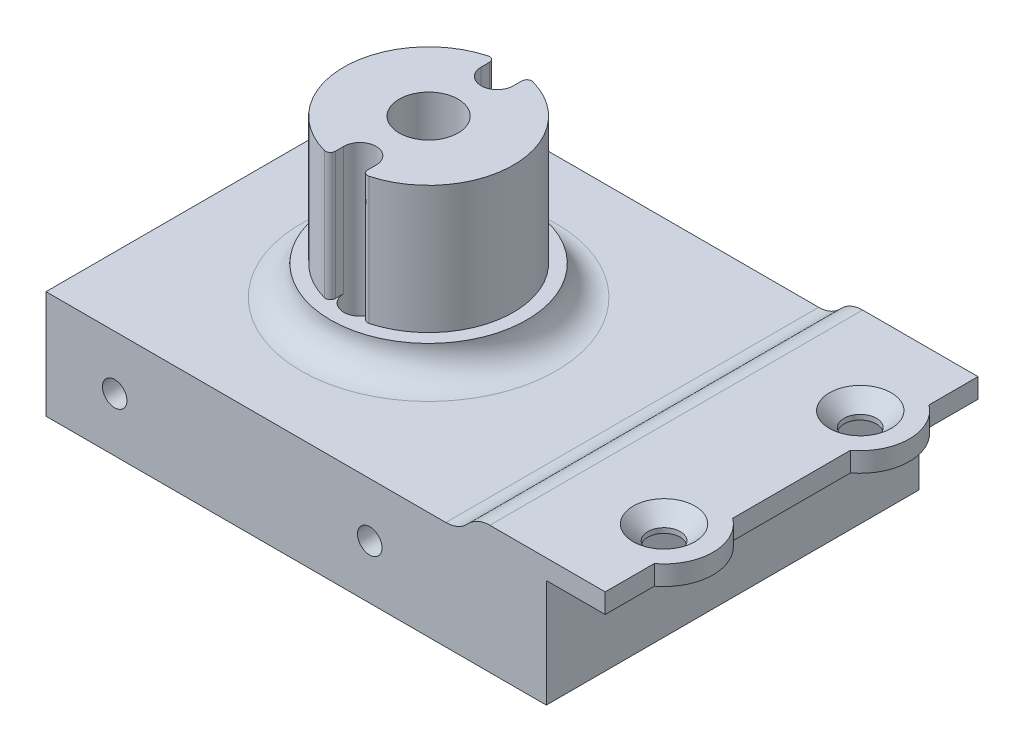
SolidWorks part; units mm, degrees
ref_plane "Спереди" through (0, 0, 0) normal (0, 0, 1) x (1, 0, 0)
ref_plane "Сверху" through (0, 0, 0) normal (0, 1, 0) x (1, 0, 0)
ref_plane "Справа" through (0, 0, 0) normal (1, 0, 0) x (0, 0, -1)
sketch "Эскиз6" plane through (0, 0, 0) normal (0, 1, 0) x (1, 0, 0)
  line L0 (-20, 0) -> (31, 0) construction
  line L1 (-20, -19) -> (31, -19)
  line L2 (-20, -19) -> (-20, 19)
  line L3 (-20, 19) -> (31, 19)
  line L4 (31, -19) -> (31, 19)
  line L5 (0, -19) -> (0, 19) construction
  dimension "D1" = 31
  dimension "D2" = 20
  dimension "D3" = 38
extrude "тело" add sketch "Эскиз6" along normal blind 11
sketch "Эскиз10" plane through (0, 11, 0) normal (0, 1, 0) x (1, 0, 0)
  circle A0 centre (0, 0) radius 10
  dimension "D1" = 20
extrude "основание оси" add sketch "Эскиз10" along normal blind 3
fillet "Скругление1" radius 3 1 edges at (0, 11, -10)
sketch "Эскиз13" plane through (0, 0, 19) normal (0, 0, 1) x (1, 0, 0)
  line L0 (31, 5.5) -> (-13, 5.5) construction
  line L1 (31, 11) -> (31, 0) construction
  line L2 (0, 0) -> (0, 11) construction
  line L3 (-20, 11) -> (31, 11) construction
  circle A0 centre (-13, 5.5) radius 1.25
  circle A1 centre (13, 5.5) radius 1.25
  dimension "D1" = 2.5
  dimension "D2" = 26
  dimension "D3" = 18
extrude "отверстия под шурупы" cut sketch "Эскиз13" against normal through all
sketch "Эскиз15" plane through (0, 14, 0) normal (0, 1, 0) x (1, 0, 0)
  circle A0 centre (0, 0) radius 8.65
  dimension "D1" = 17.3
extrude "ось" add sketch "Эскиз15" along normal blind 13
sketch "Эскиз16" plane through (0, 27, 0) normal (0, 1, 0) x (1, 0, 0)
  line L0 (-7, 1.65) -> (-8.4912, 1.65) construction
  line L1 (-7, -1.65) -> (-8.4912, -1.65) construction
  line L2 (-1.65, 7) -> (-1.65, 8.4912)
  line L3 (1.65, 7) -> (1.65, 8.4912)
  line L4 (7, 1.65) -> (8.4912, 1.65) construction
  line L5 (7, -1.65) -> (8.4912, -1.65) construction
  line L6 (1.65, -7) -> (1.65, -8.4912)
  line L8 (-1.65, -7) -> (-1.65, -8.4912)
  circle A0 centre (0, 0) radius 7 construction
  arc A1 (-1.65, 7) -> (1.65, 7) centre (0, 7) ccw
  arc A2 (7, 1.65) -> (7, -1.65) centre (7, 0) ccw construction
  arc A3 (1.65, -7) -> (-1.65, -7) centre (0, -7) ccw
  arc A4 (-7, -1.65) -> (-7, 1.65) centre (-7, 0) ccw construction
  arc A5 (-8.4912, 1.65) -> (-8.4912, -1.65) centre (0, 0) ccw construction
  circle A6 centre (0, 0) radius 8.65 construction
  arc A7 (1.65, 8.4912) -> (-1.65, 8.4912) centre (0, 0) ccw
  arc A8 (8.4912, -1.65) -> (8.4912, 1.65) centre (0, 0) ccw construction
  arc A9 (-1.65, -8.4912) -> (1.65, -8.4912) centre (0, 0) ccw
  dimension "D1" = 14
  dimension "D2" = 1.65
extrude "крепление к серве" cut sketch "Эскиз16" against normal up to surface (13 mm away) up to face at (0, 14, 8.65)
sketch "Эскиз26" plane through (0, 14, 0) normal (0, 1, 0) x (1, 0, 0)
  circle A0 centre (0, 7) radius 1.65
  circle A1 centre (0, -7) radius 1.65
  arc A2 (1.65, -7) -> (-1.65, -7) centre (0, -7) ccw construction
extrude "продолжение креплений" cut sketch "Эскиз26" against normal through all
chamfer "Фаска7" distance 2 angle 45 2 edges at (0, 0, -5.35) (0, 0, 8.65)
sketch "Эскиз17" plane through (0, 27, 0) normal (0, 1, 0) x (1, 0, 0)
  circle A0 centre (0, 0) radius 3
  dimension "D1" = 6
extrude "отверстие под болтик" cut sketch "Эскиз17" against normal through all
sketch "Эскиз24" [suppressed] plane through (0, 11, 0) normal (0, 1, 0) x (1, 0, 0)
  line L0 (31, 19) -> (-20, 19) construction
  line L1 (-15, 19) -> (15, 19)
  line L2 (-15, 19) -> (-15, -19)
  line L3 (-15, -19) -> (15, -19)
  line L4 (15, 19) -> (15, -19)
  line L5 (-20, -19) -> (31, -19) construction
  line L6 (0, 19) -> (0, -19) construction
  dimension "D1" = 30
extrude "крепление к арке" [suppressed] add sketch "Эскиз24" along normal blind 15
sketch "Эскиз27" [suppressed] plane through (-15, 0, 0) normal (-1, 0, 0) x (0, 0, 1)
  line L0 (0, 11) -> (0, 26) construction
  line L1 (-19, 11) -> (19, 11) construction
  line L2 (-19, 26) -> (19, 26) construction
  line L3 (-12.5, 18.5) -> (12.5, 18.5) construction
  circle A0 centre (-12.5, 18.5) radius 1.65
  circle A1 centre (12.5, 18.5) radius 1.65
  dimension "D2" = 3.3
  dimension "D1" = 25
  dimension "D3" = 7.5
extrude "отверстия под болты" [suppressed] cut sketch "Эскиз27" against normal through all
sketch "Эскиз19" plane through (0, 11, 0) normal (0, 1, 0) x (1, 0, 0)
  line L0 (-20, -19) -> (31, -19) construction
  line L1 (37, 19) -> (23, 19)
  line L2 (37, 19) -> (37, -19)
  line L3 (37, -19) -> (23, -19)
  line L4 (23, 19) -> (23, -19)
  line L5 (31, 19) -> (31, -19) construction
  line L6 (31, -19) -> (31, 19) construction
  dimension "D1" = 6
  dimension "D2" = 8
extrude "выступ прикрутиться к колену" add sketch "Эскиз19" along normal blind 2
sketch "Эскиз20" plane through (0, 13, 0) normal (0, 1, 0) x (1, 0, 0)
  line L0 (34, 19) -> (34, -19) construction
  line L1 (37, 19) -> (23, 19) construction
  line L2 (23, -19) -> (37, -19) construction
  line L3 (37, -19) -> (37, 19) construction
  line L4 (23, 0) -> (37, 0) construction
  line L5 (23, 19) -> (23, -19) construction
  circle A0 centre (34, 10) radius 1.65
  circle A1 centre (34, -10) radius 1.65
  dimension "D3" = 3.3
  dimension "D1" = 3
  dimension "D2" = 20
extrude "шурупы сверху" cut sketch "Эскиз20" against normal through all
sketch "Эскиз23" plane through (0, 13, 0) normal (0, 1, 0) x (1, 0, 0)
  circle A0 centre (34, 10) radius 5
  circle A1 centre (34, -10) radius 5
  circle A2 centre (34, 10) radius 1.65
  circle A3 centre (34, -10) radius 1.65
  circle A4 centre (34, -10) radius 1.65 construction
  circle A5 centre (34, 10) radius 1.65 construction
  dimension "D1" = 10
extrude "наплывы" add sketch "Эскиз23" against normal up to surface (2 mm away) up to face at (34, 11, 8.35)
chamfer "Фаска4" distance 1 angle 45 2 edges at (23, 11, 0) (23, 13, 0)
fillet "Скругление7" radius 3 2 edges at (22, 11, 0) (24, 13, 0)
chamfer "Фаска6" distance 1.5 angle 45 2 edges at (34, 13, 11.65) (34, 13, -8.35)
fillet "Скругление8" radius 0.5 4 edges at (-1.65, 20.5, -8.4912) (1.65, 20.5, -8.4912) (-1.65, 20.5, 8.4912) (1.65, 20.5, 8.4912)
